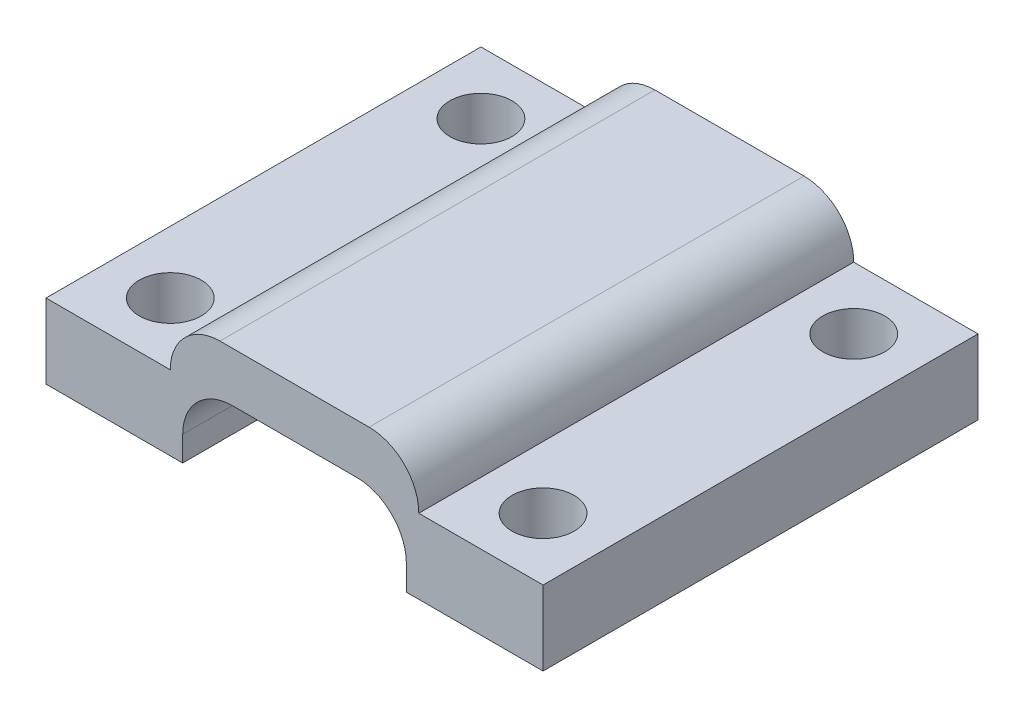
SolidWorks part; units mm, degrees
ref_plane "Front Plane" through (0, 0, 0) normal (0, 0, 1) x (1, 0, 0)
ref_plane "Top Plane" through (0, 0, 0) normal (0, 1, 0) x (1, 0, 0)
ref_plane "Right Plane" through (0, 0, 0) normal (1, 0, 0) x (0, 0, -1)
sketch "Sketch1" plane through (0, 0, 0) normal (0, 1, 0) x (1, 0, 0)
  line L1 (-12.2135, 8.3854) -> (27.7865, 8.3854)
  line L2 (-12.2135, 8.3854) -> (-12.2135, -26.6146)
  line L3 (-12.2135, -26.6146) -> (27.7865, -26.6146)
  line L4 (27.7865, 8.3854) -> (27.7865, -26.6146)
  dimension "D1" = 40
  dimension "D2" = 35
extrude "Boss-Extrude1" add sketch "Sketch1" along normal blind 6
sketch "Sketch2" plane through (0, 6, 0) normal (0, 1, 0) x (1, 0, 0)
  line L0 (-12.2135, 8.3854) -> (-12.2135, -26.6146) construction
  line L1 (27.7865, 8.3854) -> (-12.2135, 8.3854) construction
  line L2 (27.7865, -26.6146) -> (27.7865, 8.3854) construction
  circle A1 centre (-7.2135, -21.6146) radius 2.5
  circle A2 centre (22.7865, 3.3854) radius 2.5
  circle A3 centre (22.7865, -21.6146) radius 2.5
  circle A4 centre (-7.2135, 3.3854) radius 2.5
  dimension "D1" = 5
  dimension "D2" = 5
  dimension "D3" = 30
  dimension "D4" = 25
  dimension "D5" = 5
  dimension "D6" = 5
  dimension "D7" = 30
  dimension "D8" = 25
extrude "Cut-Extrude1" cut sketch "Sketch2" against normal blind 6
sketch "Sketch3" plane through (0, 6, 0) normal (0, 1, 0) x (1, 0, 0)
  line L0 (27.7865, 8.3854) -> (-12.2135, 8.3854) construction
  line L1 (-2.2135, 8.3854) -> (17.7865, 8.3854)
  line L2 (-2.2135, 8.3854) -> (-2.2135, -26.6146)
  line L3 (-2.2135, -26.6146) -> (17.7865, -26.6146)
  line L4 (17.7865, 8.3854) -> (17.7865, -26.6146)
  line L5 (-12.2135, -26.6146) -> (27.7865, -26.6146) construction
  line L6 (-12.2135, 8.3854) -> (-12.2135, -26.6146) construction
  line L7 (27.7865, -26.6146) -> (27.7865, 8.3854) construction
  dimension "D1" = 10
  dimension "D2" = 10
extrude "Boss-Extrude2" add sketch "Sketch3" along normal blind 4
sketch "Sketch4" plane through (0, 0, 0) normal (0, -1, 0) x (1, 0, 0)
  line L0 (-12.2135, 26.6146) -> (27.7865, 26.6146) construction
  line L1 (-1.2135, 26.6146) -> (16.7865, 26.6146)
  line L2 (-1.2135, 26.6146) -> (-1.2135, -8.3854)
  line L3 (-1.2135, -8.3854) -> (16.7865, -8.3854)
  line L4 (16.7865, 26.6146) -> (16.7865, -8.3854)
  line L5 (-12.2135, -8.3854) -> (-12.2135, 26.6146) construction
  line L6 (27.7865, 26.6146) -> (27.7865, -8.3854) construction
  dimension "D1" = 11
  dimension "D2" = 11
extrude "Cut-Extrude2" cut sketch "Sketch4" against normal blind 6
fillet "Fillet2" radius 4 2 edges at (16.7865, 6, 9.1146) (-1.2135, 6, 9.1146)
fillet "Fillet3" radius 4 2 edges at (17.7865, 10, 9.1146) (-2.2135, 10, 9.1146)
